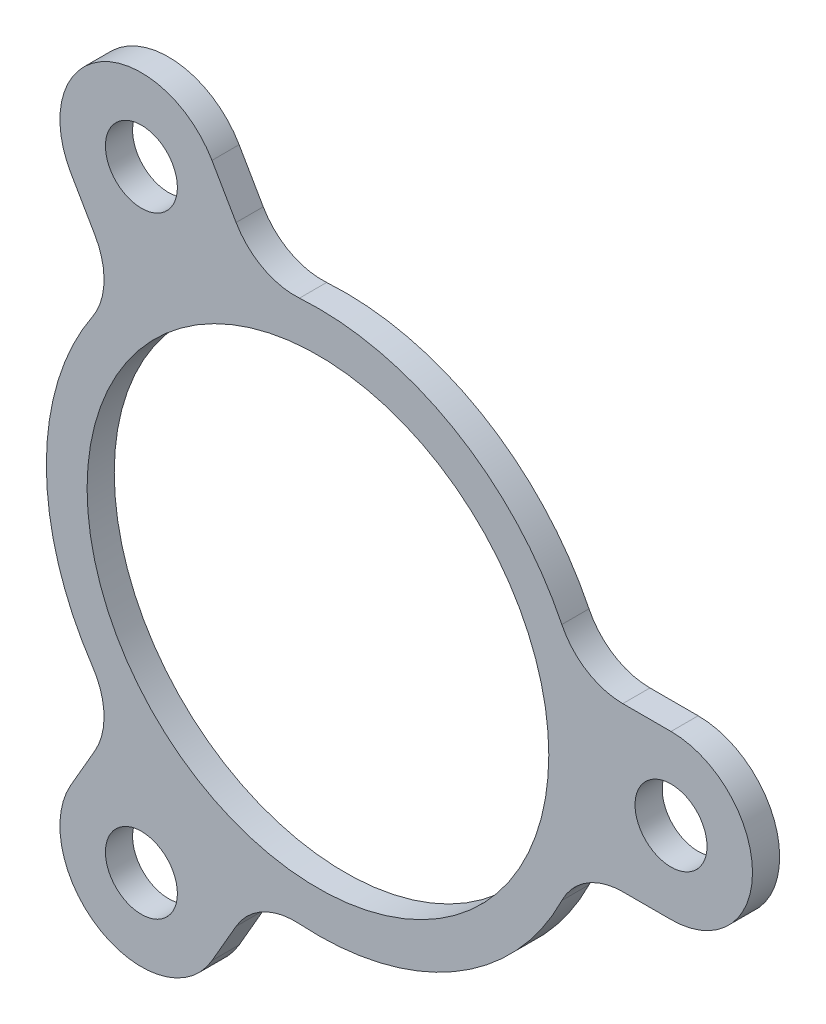
SolidWorks part; units mm, degrees
material "Alloy Steel"
ref_plane "Front Plane" through (0, 0, 0) normal (0, 0, 1) x (1, 0, 0)
ref_plane "Top Plane" through (0, 0, 0) normal (0, 1, 0) x (1, 0, 0)
ref_plane "Right Plane" through (0, 0, 0) normal (1, 0, 0) x (0, 0, -1)
ref_plane "Plane1" through (0, 0, 92) normal (0, 0, 1) x (1, 0, 0)
sketch "Sketch1" plane through (0, 0, 92) normal (0, 0, 1) x (1, 0, 0)
  line L0 (0, 0) -> (26, 0) construction
  line L1 (26, 6) -> (19.0788, 6)
  line L2 (26, -6) -> (19.0788, -6)
  line L3 (-7.8038, -25.5167) -> (-4.3432, -19.5227)
  line L4 (-18.1962, -19.5167) -> (-14.7355, -13.5227)
  line L5 (-18.1962, 19.5167) -> (-14.7355, 13.5227)
  line L6 (-7.8038, 25.5167) -> (-4.3432, 19.5227)
  circle A1 centre (26, 0) radius 3 construction
  circle A2 centre (0, 0) radius 17
  arc A4 (26, 6) -> (26, -6) centre (26, 0) cw
  arc A5 (-14.7355, 13.5227) -> (-14.7355, -13.5227) centre (0, 0) ccw
  arc A6 (-7.8038, -25.5167) -> (-18.1962, -19.5167) centre (-13, -22.5167) cw
  arc A7 (-18.1962, 19.5167) -> (-7.8038, 25.5167) centre (-13, 22.5167) cw
  arc A8 (19.0788, 6) -> (-4.3432, 19.5227) centre (0, 0) ccw
  arc A9 (-4.3432, -19.5227) -> (19.0788, -6) centre (0, 0) ccw
  point P0 (26, 0)
  point P4 (-13, -22.5167)
  point P5 (-13, 22.5167)
  point P6 (0, 0)
  point P11 (32, 0)
  dimension "D3" = 6
  dimension "D4" = 34
  dimension "D5" = 40
  dimension "D6" = 6
  dimension "D7" = 6
  dimension "D2" = 26
  dimension "D1" = 3
  dimension "D8" = 3
extrude "Boss-Extrude1" add sketch "Sketch1" along normal blind 2 contours A4 A2 region at (31.2282, 0, 92)
hole_wizard "M5 Clearance Hole1" positions "Sketch2" profile "Sketch4" hole size "M5" standard "ANSI Metric" end condition through all
sketch "Sketch2" plane through (0, 0, 94) normal (0, 0, 1) x (1, 0, 0)
  point P0 (-13, 22.5167)
  point P3 (26, 0)
  point P6 (-13, -22.5167)
sketch "Sketch4" plane through (-13, 22.5167, 94) normal (1, 0, 0) x (0, -1, 0)
  line L0 (0, 0) -> (0, 2)
  line L1 (0, 2) -> (2.65, 2)
  line L2 (2.65, 2) -> (2.65, 0)
  line L5 (2.65, 0) -> (0, 0)
  line L11 (0, -6.35) -> (0, 107.95) construction
  dimension "Thru Hole Dia." = 5.3
  dimension "Thru Hole Depth" = 2
fillet "Fillet1" radius 5 6 edges at (-4.3432, -19.5227, 93) (19.0788, -6, 93) (19.0788, 6, 93) (-4.3432, 19.5227, 93) (-14.7355, 13.5227, 93) (-14.7355, -13.5227, 93)
